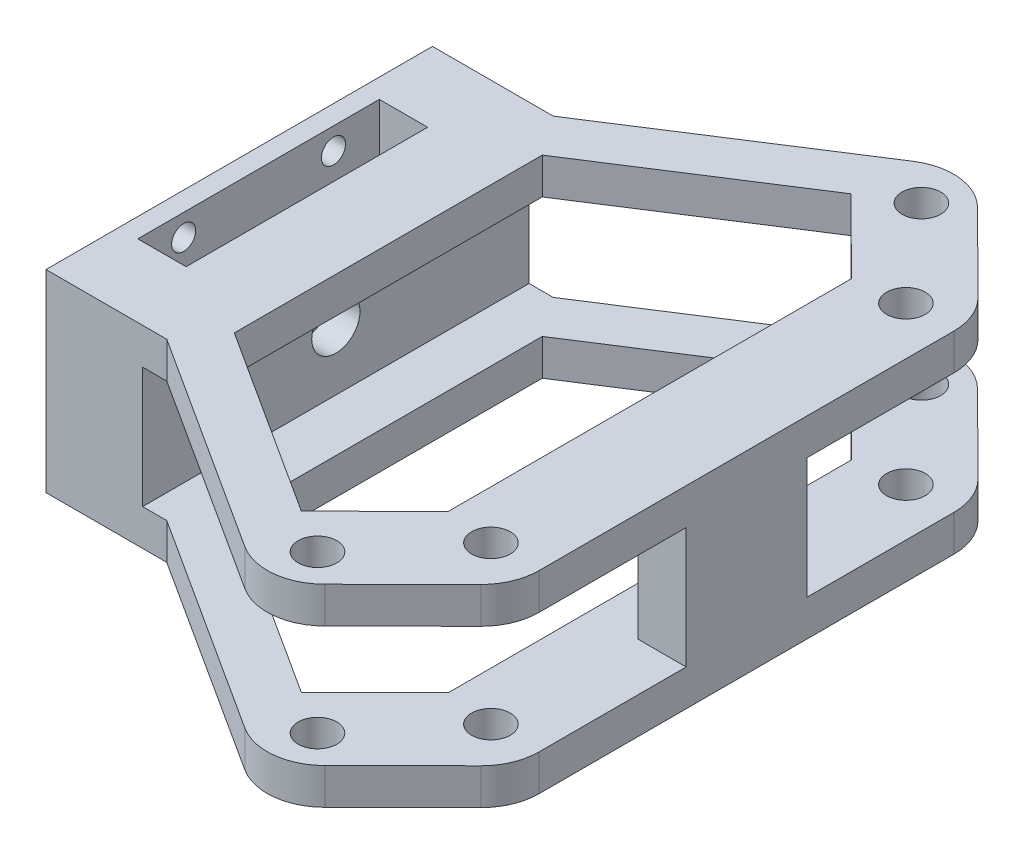
SolidWorks part; units mm, degrees
ref_plane "Front Plane" through (0, 0, 0) normal (0, 0, 1) x (1, 0, 0)
ref_plane "Top Plane" through (0, 0, 0) normal (0, 1, 0) x (1, 0, 0)
ref_plane "Right Plane" through (0, 0, 0) normal (1, 0, 0) x (0, 0, -1)
ref_plane "Plane1" through (0, -20, 0) normal (0, 1, 0) x (1, 0, 0)
sketch "Sketch1" plane through (0, -20, 0) normal (0, 1, 0) x (1, 0, 0)
  line L8 (0, 40) -> (0, -40)
  line L9 (0, -40) -> (25, -40)
  line L10 (25, -40) -> (70.3198, -69.1414)
  line L11 (85.2711, -67.5574) -> (101.4611, -51.4594)
  line L12 (105, -42.95) -> (105, 42.95)
  line L13 (4, 25) -> (4, -25)
  line L14 (4, -25) -> (14, -25)
  line L15 (14, -25) -> (14, 25)
  line L16 (30.85, -31.8727) -> (30.85, 31.8727)
  line L17 (30.85, -31.8727) -> (69.7477, -56.8846)
  line L18 (69.7477, -56.8846) -> (85, -41.719)
  line L19 (85, -41.719) -> (85, 41.719)
  line L20 (-57.75, 0) -> (57.75, 0) construction
  line L21 (69.7477, 56.8846) -> (85, 41.719)
  line L22 (30.85, 31.8727) -> (69.7477, 56.8846)
  line L23 (4, 25) -> (14, 25)
  line L24 (85.2711, 67.5574) -> (101.4611, 51.4594)
  line L25 (25, 40) -> (70.3198, 69.1414)
  line L26 (0, 40) -> (25, 40)
  circle A0 centre (78.7, -62.5) radius 4
  circle A1 centre (95.05, -42.95) radius 4
  arc A2 (101.4611, -51.4594) -> (105, -42.95) centre (93, -42.95) ccw
  arc A3 (70.3198, -69.1414) -> (85.2711, -67.5574) centre (76.81, -59.048) ccw
  arc A4 (70.3198, 69.1414) -> (85.2711, 67.5574) centre (76.81, 59.048) cw
  arc A5 (101.4611, 51.4594) -> (105, 42.95) centre (93, 42.95) cw
  circle A6 centre (95.05, 42.95) radius 4
  circle A7 centre (78.7, 62.5) radius 4
  point P3 (105, 0)
  point P55 (85, 0)
  point P57 (30.85, 0)
  point P58 (14, 0)
  point P59 (4, 0)
  point P61 (0, 0)
  dimension "D4" = 8
  dimension "D15" = 12
  dimension "D1" = 40
  dimension "D2" = 25
  dimension "D3" = 15
  dimension "D5" = 4
  dimension "D6" = 10
  dimension "D7" = 105
  dimension "D8" = 20
  dimension "D9" = 54.15
  dimension "D10" = 53.7
  dimension "D11" = 22.5
  dimension "D12" = 42.95
  dimension "D13" = 16.35
  dimension "D14" = 10
extrude "Boss-Extrude1" add sketch "Sketch1" along normal blind 7.5
sketch "Sketch3" plane through (0, -12.5, 0) normal (0, 1, 0) x (1, 0, 0)
  line L1 (105, -42.95) -> (105, 42.95) construction
  line L2 (105, 12.5) -> (95, 12.5)
  line L3 (95, 12.5) -> (95, -12.5)
  line L4 (95, -12.5) -> (105, -12.5)
  line L6 (105, 12.5) -> (105, -12.5)
  line L7 (0, 40) -> (20, 40)
  line L8 (25, 40) -> (0, 40) construction
  line L9 (20, 40) -> (20, -40)
  line L10 (0, -40) -> (25, -40) construction
  line L11 (20, -40) -> (0, -40)
  line L12 (0, -40) -> (0, 40)
  line L13 (4, 25) -> (14, 25)
  line L14 (14, 25) -> (14, -25)
  line L15 (14, -25) -> (4, -25)
  line L16 (4, -25) -> (4, 25)
  point P4 (105, 0)
  dimension "D1" = 10
  dimension "D2" = 25
  dimension "D3" = 20
extrude "Boss-Extrude2" add sketch "Sketch3" along normal blind 25
pattern_linear "LPattern1" count 2 spacing 32.5 along (0, 1, 0) of "Boss-Extrude1"
sketch "Sketch4" plane through (0, 0, 0) normal (-1, 0, 0) x (0, 0, 1)
  line L2 (-15.5, -15.5) -> (15.5, -15.5) construction
  line L3 (-15.5, -15.5) -> (-15.5, 15.5) construction
  line L4 (-15.5, 15.5) -> (15.5, 15.5) construction
  line L5 (15.5, -15.5) -> (15.5, 15.5) construction
  line L6 (-15.5, -15.5) -> (15.5, 15.5) construction
  line L7 (-15.5, 15.5) -> (15.5, -15.5) construction
  circle A0 centre (0, 0) radius 12.5
  circle A1 centre (0, 0) radius 5
  circle A6 centre (15.5, 15.5) radius 2.5
  circle A7 centre (-15.5, 15.5) radius 2.5
  circle A8 centre (-15.5, -15.5) radius 2.5
  circle A9 centre (15.5, -15.5) radius 2.5
  dimension "D1" = 25
  dimension "D2" = 10
  dimension "D3" = 31
  dimension "D5" = 5
  dimension "D4" = 31
extrude "Cut-Extrude1" cut sketch "Sketch4" against normal blind 3 contours A0
extrude "Cut-Extrude2" cut sketch "Sketch4<3>" against normal blind 40 contours A1
sketch "Sketch4<3>" plane through (0, 0, 0) normal (-1, 0, 0) x (0, 0, 1) same geometry as "Sketch4"
extrude "Cut-Extrude3" cut sketch "Sketch4<4>" against normal blind 4 contours A8 | A6 | A7 | A9
sketch "Sketch4<4>" plane through (0, 0, 0) normal (-1, 0, 0) x (0, 0, 1) same geometry as "Sketch4"
sketch "Sketch5" plane through (95, 0, 0) normal (-1, 0, 0) x (0, 0, 1)
  line L0 (-15.5, -15.5) -> (15.5, 15.5) construction
  circle A0 centre (0, 0) radius 5
  dimension "D1" = 10
extrude "Cut-Extrude4" cut sketch "Sketch5" against normal blind 5
